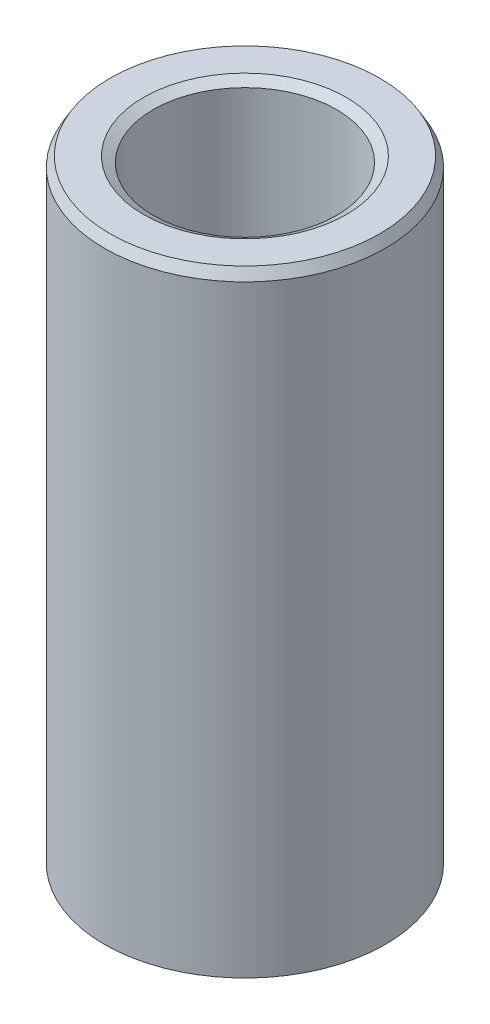
SolidWorks part; units mm, degrees
ref_plane "Front Plane" through (0, 0, 0) normal (0, 0, 1) x (1, 0, 0)
ref_plane "Top Plane" through (0, 0, 0) normal (0, 1, 0) x (1, 0, 0)
ref_plane "Right Plane" through (0, 0, 0) normal (1, 0, 0) x (0, 0, -1)
sketch "Sketch1" plane through (0, 0, 0) normal (0, 1, 0) x (1, 0, 0)
  circle A0 centre (0, 0) radius 27.5
  dimension "SLEEVE_OD" = 55
extrude "Boss-Extrude1" add sketch "Sketch1" along normal blind 121.05
sketch "Sketch2" plane through (0, 0, 0) normal (0, 1, 0) x (1, 0, 0)
  circle A0 centre (0, 0) radius 17.9506
  dimension "BORE_D" = 35.9012
extrude "Cut-Extrude1" cut sketch "Sketch2" along normal through all
chamfer "Chamfer1" distance 1.9146 angle 30 4 edges at (0, 121.05, 17.9506) (0, 0, 17.9506) (0, 0, 27.5) (0, 121.05, 27.5) first distance on face at (0, 121.05, 17.9506) first distance on face at (0, 0, 17.9506) first distance on face at (0, 121.05, 27.5)
